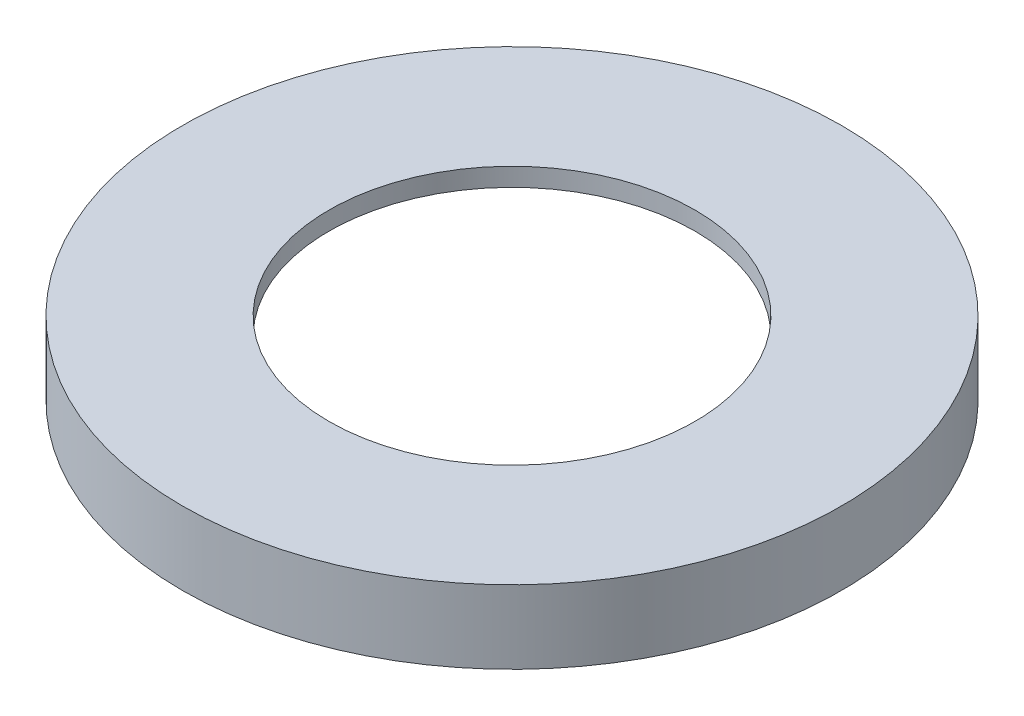
SolidWorks part; units mm, degrees
ref_plane "Front Plane" through (0, 0, 0) normal (0, 0, 1) x (1, 0, 0)
ref_plane "Top Plane" through (0, 0, 0) normal (0, 1, 0) x (1, 0, 0)
ref_plane "Right Plane" through (0, 0, 0) normal (1, 0, 0) x (0, 0, -1)
sketch "Sketch1" plane through (0, 0, 0) normal (0, 1, 0) x (1, 0, 0)
  circle A0 centre (0, 0) radius 15.5
  circle A1 centre (0, 0) radius 18
extrude "Boss-Extrude1" add sketch "Sketch1" along normal blind 3
sketch "Sketch2" plane through (0, 3, 0) normal (0, 1, 0) x (1, 0, 0)
  circle A0 centre (0, 0) radius 18
  circle A1 centre (0, 0) radius 10
extrude "Boss-Extrude2" add sketch "Sketch2" along normal blind 1
thread "Thread2" pitch 1 method cut trim with start face yes trim with end face yes profile "Thread Profile2" start angle 0, offset 1, length 0, pitch 1, diameter 31
ref_plane "Plane2" through (15.5, -1, 0) normal (0, 0, 1) x (1, 0, 0)
sketch "Thread Profile2" plane through (15.5, -1, 0) normal (0, 0, 1) x (1, 0, 0)
  line L0 (0, 0) -> (0, 1) construction
  line L1 (0, 0) -> (0.5413, 0.3125)
  line L2 (0.5413, 0.3125) -> (0.5413, 0.4375)
  line L3 (0.5413, 0.4375) -> (0, 0.75)
  line L4 (0.5413, 0.375) -> (0, 0.375) construction
  line L11 (0, 0) -> (0, 0.75)
  point P2 (0, 0)
  dimension "Pitch" = 1
  dimension "Profile_Angle" = 60
  dimension "Profile_Land" = 0.125
  dimension "Profile_Height" = 0.5413
